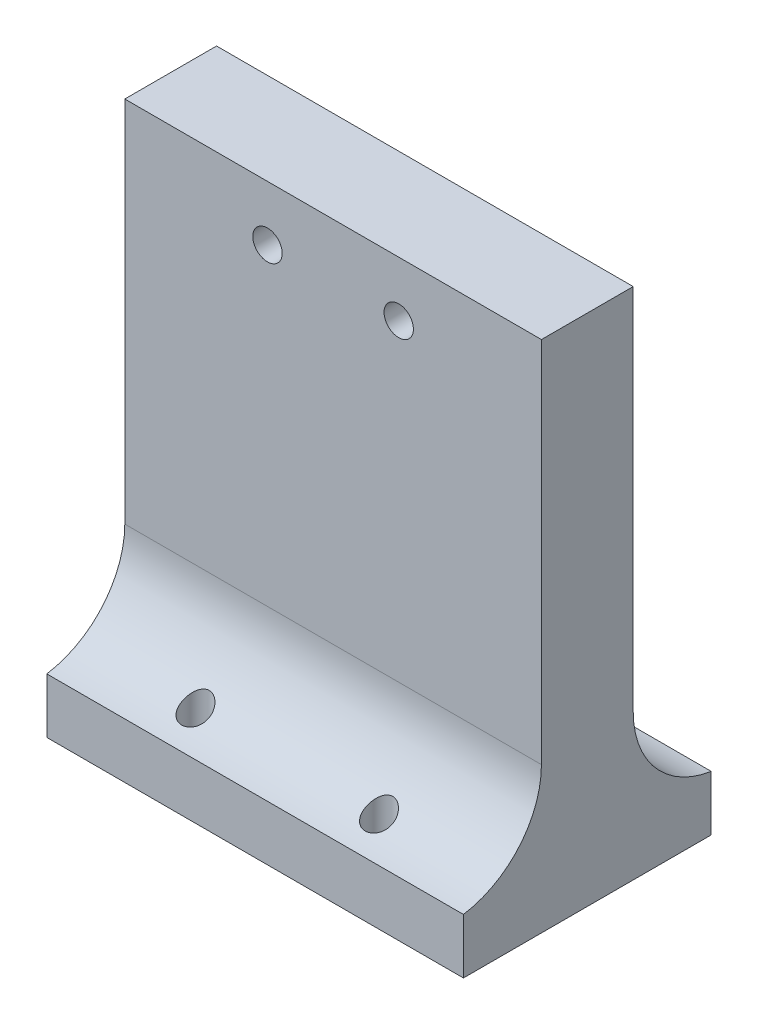
SolidWorks part; units mm, degrees
ref_plane "Płaszczyzna przednia" through (0, 0, 0) normal (0, 0, 1) x (1, 0, 0)
ref_plane "Płaszczyzna górna" through (0, 0, 0) normal (0, 1, 0) x (1, 0, 0)
ref_plane "Płaszczyzna prawa" through (0, 0, 0) normal (1, 0, 0) x (0, 0, -1)
sketch "Sketch1" plane through (0, 0, 0) normal (0, 1, 0) x (1, 0, 0)
  line L1 (0, 0) -> (45.4, 0)
  line L2 (0, 0) -> (0, 27)
  line L3 (0, 27) -> (45.4, 27)
  line L4 (45.4, 0) -> (45.4, 27)
  dimension "D1" = 45.4
  dimension "D2" = 27
extrude "Boss-Extrude1" add sketch "Sketch1" along normal blind 6
sketch "Sketch4" plane through (0, 6, 0) normal (0, 1, 0) x (1, 0, 0)
  line L0 (0, 27) -> (0, 0) construction
  line L1 (0, 18.5) -> (45.4, 18.5)
  line L2 (0, 18.5) -> (0, 8.5)
  line L3 (0, 8.5) -> (45.4, 8.5)
  line L4 (45.4, 18.5) -> (45.4, 8.5)
  line L5 (45.4, 0) -> (45.4, 27) construction
  line L6 (0, 0) -> (45.4, 0) construction
  dimension "D1" = 10
  dimension "D2" = 8.5
extrude "Boss-Extrude2" add sketch "Sketch4" along normal blind 50
fillet "Fillet3" radius 10 2 edges at (22.7, 6, -8.5) (22.7, 6, -18.5)
ref_plane "Plane3" through (0, 15.8869, 0) normal (0, -1, 0) x (-1, 0, 0)
hole_wizard "Ø3.0mm Dowel Hole1" positions "Sketch2" profile "Sketch3" hole size "Ø3.0" standard "ANSI Metric" end condition up to next
sketch "Sketch2" plane through (0, 15.8869, 0) normal (0, 1, 0) x (1, 0, 0)
  point P0 (12.7, 23.5)
  point P2 (32.7, 23.5)
  point P4 (32.7, 3.5)
  point P6 (12.7, 3.5)
  dimension "D1" = 20
  dimension "D2" = 20
  dimension "D3" = 20
sketch "Sketch3" plane through (12.7, 15.8869, -23.5) normal (1, 0, 0) x (0, 0, 1)
  line L0 (0, 0) -> (0, 15.8869)
  line L1 (0, 15.8869) -> (1.5, 15.8869)
  line L2 (1.5, 15.8869) -> (1.5, 0)
  line L5 (1.5, 0) -> (0, 0)
  line L11 (0, -6.35) -> (0, 107.95) construction
  dimension "Thru Hole Dia." = 3
  dimension "Thru Hole Depth" = 15.8869
ref_plane "Plane4" through (22.7, 0, 0) normal (1, 0, 0) x (0, 0, -1)
hole_wizard "Ø3.0mm Dowel Hole2" positions "Sketch6" profile "Sketch7" hole size "Ø3.0" standard "ANSI Metric" end condition up to next
sketch "Sketch6" plane through (0, 0, -18.5) normal (0, 0, -1) x (-1, 0, 0)
  line L2 (-45.4, 56) -> (0, 56) construction
  point P0 (-29.85, 50)
  point P2 (-15.55, 50)
  dimension "D1" = 14.3
  dimension "D3" = 6
sketch "Sketch7" plane through (29.85, 50, -18.5) normal (1, 0, 0) x (0, 1, 0)
  line L0 (0, 0) -> (0, 10)
  line L1 (0, 10) -> (1.6, 10)
  line L2 (1.6, 10) -> (1.6, 0)
  line L5 (1.6, 0) -> (0, 0)
  line L11 (0, -6.35) -> (0, 107.95) construction
  dimension "Thru Hole Dia." = 3.2
  dimension "Thru Hole Depth" = 10
